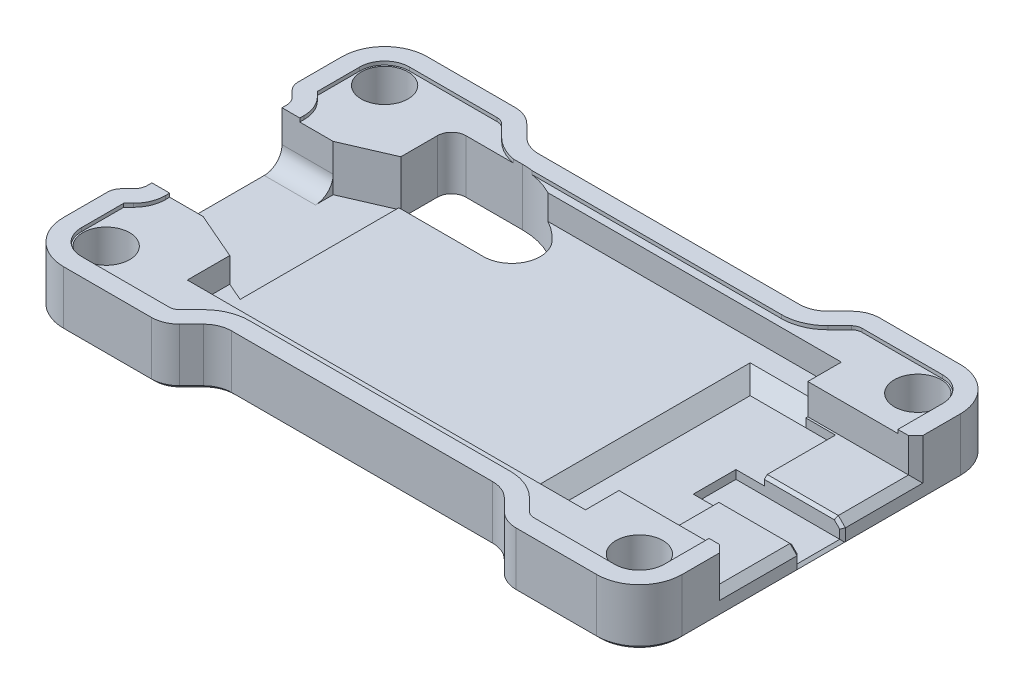
SolidWorks part; units mm, degrees
ref_plane "Front Plane" through (0, 0, 0) normal (0, 0, 1) x (1, 0, 0)
ref_plane "Top Plane" through (0, 0, 0) normal (0, 1, 0) x (1, 0, 0)
ref_plane "Right Plane" through (0, 0, 0) normal (1, 0, 0) x (0, 0, -1)
sketch "Sketch1" plane through (0, 0, 0) normal (0, 1, 0) x (1, 0, 0)
  line L0 (0, -5.29) -> (0, 5.29)
  line L1 (0, 5.29) -> (-1, 6.29)
  line L2 (-1, 6.29) -> (-1, 12.79)
  line L3 (-1, 12.79) -> (9, 12.79)
  line L4 (9, 12.79) -> (11, 10.79)
  line L5 (11, 10.79) -> (31, 10.79)
  line L6 (31, 10.79) -> (33, 12.79)
  line L7 (33, 12.79) -> (42.5, 12.79)
  line L8 (42.5, 12.79) -> (42.5, 6.64)
  line L9 (42.5, 6.64) -> (33.85, 6.64)
  line L10 (33.85, 6.64) -> (33.85, -6.64)
  line L11 (0, 0) -> (36.6809, 0) construction
  line L12 (42.5, -6.64) -> (33.85, -6.64)
  line L13 (42.5, -12.79) -> (42.5, -6.64)
  line L14 (33, -12.79) -> (42.5, -12.79)
  line L15 (31, -10.79) -> (33, -12.79)
  line L16 (11, -10.79) -> (31, -10.79)
  line L17 (9, -12.79) -> (11, -10.79)
  line L18 (-1, -12.79) -> (9, -12.79)
  line L19 (-1, -6.29) -> (-1, -12.79)
  line L20 (0, -5.29) -> (-1, -6.29)
  point P15 (33.85, 0)
  dimension "D1" = 5.29
  dimension "D2" = 1
  dimension "D3" = 1
  dimension "D4" = 6.5
  dimension "D5" = 10
  dimension "D6" = 2
  dimension "D7" = 20
  dimension "D8" = 2
  dimension "D9" = 2
  dimension "D10" = 9.5
  dimension "D11" = 6.15
  dimension "D12" = 8.65
extrude "Boss-Extrude1" add sketch "Sketch1" along normal blind 4
fillet "Fillet1" radius 3 4 edges at (-1, 2, -12.79) (42.5, 2, -12.79) (42.5, 2, 12.79) (-1, 2, 12.79)
fillet "Fillet2" radius 1 6 edges at (33.85, 2, 6.64) (33.85, 2, -6.64) (-1, 2, 6.29) (0, 2, 5.29) (0, 2, -5.29) (-1, 2, -6.29)
fillet "Fillet3" radius 2 8 edges at (33, 2, 12.79) (31, 2, 10.79) (9, 2, 12.79) (11, 2, 10.79) (33, 2, -12.79) (31, 2, -10.79) (11, 2, -10.79) (9, 2, -12.79)
sketch "Sketch2" plane through (0, 4, 0) normal (0, 1, 0) x (1, 0, 0)
  line L0 (-1, 9.79) -> (-1, 6.7042) construction
  line L1 (-0.25, -4.575) -> (7.75, -4.575)
  line L2 (-0.25, -4.575) -> (-0.25, 4.575)
  line L3 (-0.25, 4.575) -> (7.75, 4.575)
  line L4 (7.75, -4.575) -> (7.75, 4.575)
  line L5 (-0.25, -4.575) -> (7.75, 4.575) construction
  line L6 (-0.25, 4.575) -> (7.75, -4.575) construction
  point P0 (3.75, 0)
  dimension "D1" = 8.75
  dimension "D2" = 8
  dimension "D3" = 9.15
extrude "Cut-Extrude1" cut sketch "Sketch2" against normal blind 3.5
fillet "Fillet4" radius 1.25 2 edges at (3.875, 0.5, -4.575) (3.875, 0.5, 4.575)
sketch "Sketch3" plane through (0, 0, 0) normal (0, -1, 0) x (1, 0, 0)
  line L0 (42.5, 9.79) -> (42.5, 6.64) construction
  line L1 (42.5, 7.9165) -> (32.5587, 7.9165)
  line L2 (42.5, 7.9165) -> (42.5, -7.5646)
  line L3 (42.5, -7.5646) -> (32.5587, -7.5646)
  line L4 (32.5587, 7.9165) -> (32.5587, -7.5646)
extrude "Boss-Extrude2" add sketch "Sketch3" against normal blind 1.6
chamfer "Chamfer1" distance 0.5 angle 45 3 edges at (42.5, 2.8, 6.64) (42.5, 2.8, -6.64) (42.5, 1.6, 0)
sketch "Sketch4" plane through (0, 4, 0) normal (0, 1, 0) x (1, 0, 0)
  line L1 (6.9149, -9) -> (34.9149, -9)
  line L2 (6.9149, -9) -> (6.9149, 9)
  line L3 (6.9149, 9) -> (34.9149, 9)
  line L4 (34.9149, -9) -> (34.9149, 9)
  line L5 (6.9149, -9) -> (34.9149, 9) construction
  line L6 (6.9149, 9) -> (34.9149, -9) construction
  point P0 (20.9149, 0)
  dimension "D1" = 18
  dimension "D2" = 28
extrude "Cut-Extrude2" cut sketch "Sketch4" against normal blind 2
sketch "Sketch5" plane through (0, 4, 0) normal (0, 1, 0) x (1, 0, 0)
  line L0 (-1, 9.79) -> (-1, 6.7042) construction
  line L1 (8.1716, 12.79) -> (2, 12.79) construction
  line L2 (39.5, 12.79) -> (33.8284, 12.79) construction
  line L3 (42.5, 7.14) -> (42.5, 9.79) construction
  line L4 (42.5, -9.79) -> (42.5, -7.14) construction
  line L5 (33.8284, -12.79) -> (39.5, -12.79) construction
  line L6 (2, -12.79) -> (8.1716, -12.79) construction
  line L7 (-1, -6.7042) -> (-1, -9.79) construction
  circle A0 centre (2, 9.79) radius 1.65
  circle A1 centre (2, -9.79) radius 1.65
  circle A2 centre (39.5, 9.79) radius 1.65
  circle A3 centre (39.5, -9.79) radius 1.65
  dimension "D1" = 3
  dimension "D3" = 3
  dimension "D4" = 3
  dimension "D5" = 3
  dimension "D6" = 3
  dimension "D7" = 3
  dimension "D8" = 3
  dimension "D9" = 3.3
  dimension "D10" = 3.3
  dimension "D11" = 3.3
  dimension "D12" = 3.3
  dimension "D2" = 3
extrude "Cut-Extrude3" cut sketch "Sketch5" against normal through all
sketch "Sketch6" plane through (42.5, 0, 0) normal (1, 0, 0) x (0, 0, -1)
  line L0 (5.64, 2) -> (-5.64, 2) construction
  line L1 (-1.5, 0.4) -> (1.5, 0.4)
  line L2 (-1.5, 0.4) -> (-1.5, 3.6)
  line L3 (-1.5, 3.6) -> (1.5, 3.6)
  line L4 (1.5, 0.4) -> (1.5, 3.6)
  line L5 (-1.5, 0.4) -> (1.5, 3.6) construction
  line L6 (-1.5, 3.6) -> (1.5, 0.4) construction
  line L7 (-9.79, 0) -> (9.79, 0) construction
  point P0 (0, 2)
  dimension "D1" = 0.4
  dimension "D2" = 3
extrude "Cut-Extrude4" cut sketch "Sketch6" against normal blind 7.5
chamfer "Chamfer2" distance 0.2 angle 45 7 edges at (38.5, 1.6, -1.5) (42.25, 1.35, -1.5) (42.5, 0.75, -1.5) (42.5, 0.4, 0) (42.5, 0.75, 1.5) (42.25, 1.35, 1.5) (38.5, 1.6, 1.5)
chamfer "Chamfer3" distance 0.25 angle 45 32 edges at (-0.5, 0, -5.79) (-0.0761, 0, -5.2585) (-0.9239, 0, -6.3215) (0, 0, 0) (-1, 0, -8.2471) (-0.0761, 0, 5.2585) (-0.1213, 0, -11.9113) (-0.5, 0, 5.79) (5.0858, 0, -12.79) (-0.9239, 0, 6.3215) (8.9369, 0, -12.6378) (-1, 0, 8.2471) (10, 0, -11.79) (-0.1213, 0, 11.9113) (11.0631, 0, -10.9422) (5.0858, 0, 12.79) (21, 0, -10.79) (8.9369, 0, 12.6378) (30.9369, 0, -10.9422) (10, 0, 11.79) (32, 0, -11.79) (11.0631, 0, 10.9422) (33.0631, 0, -12.6378) (21, 0, 10.79) (36.6642, 0, -12.79) (30.9369, 0, 10.9422) (41.6213, 0, -11.9113) (32, 0, 11.79) (42.5, 0, 0) (33.0631, 0, 12.6378) (41.6213, 0, 11.9113) (36.6642, 0, 12.79)
sketch "Sketch7" plane through (0, 2, 0) normal (0, 1, 0) x (1, 0, 0)
  line L0 (30.1716, 10.79) -> (11.8284, 10.79) construction
  line L1 (6.9149, 9.59) -> (16.9149, 9.59)
  line L2 (6.9149, 9.59) -> (6.9149, 4.59)
  line L3 (6.9149, 4.59) -> (16.9149, 4.59)
  line L4 (16.9149, 9.59) -> (16.9149, 4.59)
  line L5 (6.9149, 9) -> (6.9149, 4.575) construction
  dimension "D1" = 1.2
  dimension "D2" = 0
  dimension "D3" = 10
  dimension "D4" = 5
extrude "Cut-Extrude5" cut sketch "Sketch7" against normal through all both and the other way through all
fillet "Fillet5" radius 5 1 edges at (16.9149, 2, -9.59)
fillet "Fillet6" radius 2 1 edges at (16.9149, 1, -4.59)
fillet "Fillet7" radius 1 2 edges at (6.9149, 1, -4.59) (6.9149, 2, -9.59)
sketch "Sketch8" plane through (0, 4, 0) normal (0, 1, 0) x (1, 0, 0)
  line L0 (3.5977, 4.575) -> (8.2021, 6.575)
  line L1 (6.9149, 4.575) -> (0, 4.575) construction
  line L2 (8.2021, 6.575) -> (8.2021, -6.575)
  line L4 (3.5977, -4.575) -> (3.5977, 4.575)
  line L5 (3.5977, -4.575) -> (8.2021, -6.575)
  point P6 (3.5977, 0)
  dimension "D1" = 2
  dimension "D2" = 2
  dimension "D3" = 9.15
sketch "Sketch9" plane through (0, 2, 0) normal (0, 1, 0) x (1, 0, 0)
  line L0 (42.5, 7.14) -> (42.5, 1.7) construction
  line L1 (33, -6.5) -> (37, -6.5)
  line L2 (33, -6.5) -> (33, 6.5)
  line L3 (33, 6.5) -> (37, 6.5)
  line L4 (37, -6.5) -> (37, 6.5)
  line L5 (33, -6.5) -> (37, 6.5) construction
  line L6 (33, 6.5) -> (37, -6.5) construction
  point P0 (35, 0)
  dimension "D1" = 5.5
  dimension "D2" = 9.5
  dimension "D3" = 13
extrude "Cut-Extrude8" cut sketch "Sketch9" against normal blind 1
chamfer "Chamfer4" distance 3 angle 45 1 edges at (33, 2, 0)
chamfer "Chamfer5" distance 1 angle 45 2 edges at (32.1699, 2, 6.5) (32.1699, 2, -6.5)
extrude "Cut-Extrude9" cut sketch "Sketch8" against normal up to surface (3.5 mm away) up to face at (3.875, 0.5, 0)
sketch "Sketch11" plane through (0, 4, 0) normal (0, 1, 0) x (1, 0, 0)
  line L100 (0.25, 6.8078) -> (0.591, 6.4668)
  line L101 (0.25, 9.79) -> (0.25, 6.8078)
  line L102 (8.1716, 11.54) -> (2, 11.54)
  line L103 (9.5303, 10.4919) -> (8.7019, 11.3203)
  line L104 (30.1716, 9.54) -> (11.8284, 9.54)
  line L105 (33.2981, 11.3203) -> (32.4697, 10.4919)
  line L106 (39.5, 11.54) -> (33.8284, 11.54)
  line L107 (41.25, -9.79) -> (41.25, 9.79)
  line L108 (33.8284, -11.54) -> (39.5, -11.54)
  line L109 (32.4697, -10.4919) -> (33.2981, -11.3203)
  line L110 (11.8284, -9.54) -> (30.1716, -9.54)
  line L111 (8.7019, -11.3203) -> (9.5303, -10.4919)
  line L112 (2, -11.54) -> (8.1716, -11.54)
  line L113 (0.25, -6.8078) -> (0.25, -9.79)
  line L114 (0.591, -6.4668) -> (0.25, -6.8078)
  line L115 (1.25, 4.8758) -> (1.25, -4.8758)
  line L116 (0.25, 6.8078) -> (0.591, 6.4668)
  line L117 (0.25, 9.79) -> (0.25, 6.8078)
  line L118 (8.1716, 11.54) -> (2, 11.54)
  line L119 (9.5303, 10.4919) -> (8.7019, 11.3203)
  line L120 (30.1716, 9.54) -> (11.8284, 9.54)
  line L121 (33.2981, 11.3203) -> (32.4697, 10.4919)
  line L122 (39.5, 11.54) -> (33.8284, 11.54)
  line L123 (41.25, -9.79) -> (41.25, 9.79)
  line L124 (33.8284, -11.54) -> (39.5, -11.54)
  line L125 (32.4697, -10.4919) -> (33.2981, -11.3203)
  line L126 (11.8284, -9.54) -> (30.1716, -9.54)
  line L127 (8.7019, -11.3203) -> (9.5303, -10.4919)
  line L128 (2, -11.54) -> (8.1716, -11.54)
  line L129 (0.25, -6.8078) -> (0.25, -9.79)
  line L130 (0.591, -6.4668) -> (0.25, -6.8078)
  line L131 (1.25, 4.8758) -> (1.25, -4.8758)
  arc A72 (1.25, 4.8758) -> (0.591, 6.4668) centre (-1, 4.8758) ccw
  arc A73 (2, 11.54) -> (0.25, 9.79) centre (2, 9.79) ccw
  arc A74 (8.7019, 11.3203) -> (8.1716, 11.54) centre (8.1716, 10.79) ccw
  arc A75 (9.5303, 10.4919) -> (11.8284, 9.54) centre (11.8284, 12.79) ccw
  arc A76 (30.1716, 9.54) -> (32.4697, 10.4919) centre (30.1716, 12.79) ccw
  arc A77 (33.8284, 11.54) -> (33.2981, 11.3203) centre (33.8284, 10.79) ccw
  arc A78 (41.25, 9.79) -> (39.5, 11.54) centre (39.5, 9.79) ccw
  arc A79 (39.5, -11.54) -> (41.25, -9.79) centre (39.5, -9.79) ccw
  arc A80 (33.2981, -11.3203) -> (33.8284, -11.54) centre (33.8284, -10.79) ccw
  arc A81 (32.4697, -10.4919) -> (30.1716, -9.54) centre (30.1716, -12.79) ccw
  arc A82 (11.8284, -9.54) -> (9.5303, -10.4919) centre (11.8284, -12.79) ccw
  arc A83 (8.1716, -11.54) -> (8.7019, -11.3203) centre (8.1716, -10.79) ccw
  arc A84 (0.25, -9.79) -> (2, -11.54) centre (2, -9.79) ccw
  arc A85 (0.591, -6.4668) -> (1.25, -4.8758) centre (-1, -4.8758) ccw
  arc A86 (1.25, 4.8758) -> (0.591, 6.4668) centre (-1, 4.8758) ccw
  arc A87 (2, 11.54) -> (0.25, 9.79) centre (2, 9.79) ccw
  arc A88 (8.7019, 11.3203) -> (8.1716, 11.54) centre (8.1716, 10.79) ccw
  arc A89 (9.5303, 10.4919) -> (11.8284, 9.54) centre (11.8284, 12.79) ccw
  arc A90 (30.1716, 9.54) -> (32.4697, 10.4919) centre (30.1716, 12.79) ccw
  arc A91 (33.8284, 11.54) -> (33.2981, 11.3203) centre (33.8284, 10.79) ccw
  arc A92 (41.25, 9.79) -> (39.5, 11.54) centre (39.5, 9.79) ccw
  arc A93 (39.5, -11.54) -> (41.25, -9.79) centre (39.5, -9.79) ccw
  arc A94 (33.2981, -11.3203) -> (33.8284, -11.54) centre (33.8284, -10.79) ccw
  arc A95 (32.4697, -10.4919) -> (30.1716, -9.54) centre (30.1716, -12.79) ccw
  arc A96 (11.8284, -9.54) -> (9.5303, -10.4919) centre (11.8284, -12.79) ccw
  arc A97 (8.1716, -11.54) -> (8.7019, -11.3203) centre (8.1716, -10.79) ccw
  arc A98 (0.25, -9.79) -> (2, -11.54) centre (2, -9.79) ccw
  arc A99 (0.591, -6.4668) -> (1.25, -4.8758) centre (-1, -4.8758) ccw
  dimension "D1" = 1
extrude "Cut-Extrude10" cut sketch "Sketch11" against normal blind 0.25
